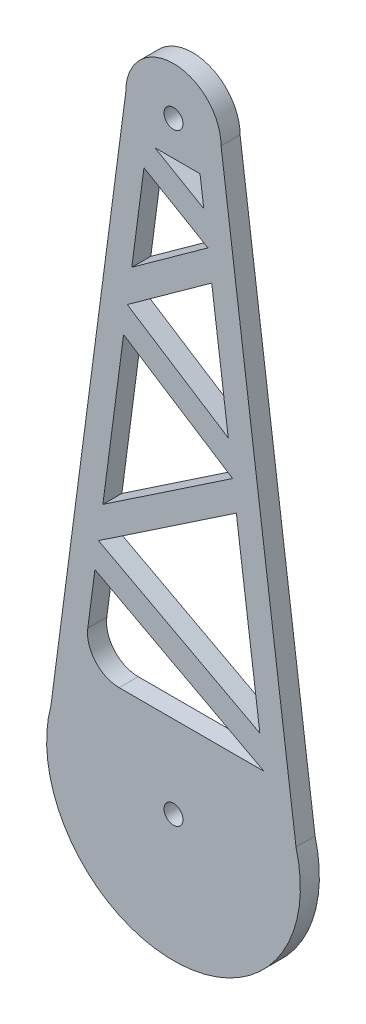
SolidWorks part; units mm, degrees
material "Alloy Steel"
ref_plane "Front Plane" through (0, 0, 0) normal (0, 0, 1) x (1, 0, 0)
ref_plane "Top Plane" through (0, 0, 0) normal (0, 1, 0) x (1, 0, 0)
ref_plane "Right Plane" through (0, 0, 0) normal (1, 0, 0) x (0, 0, -1)
sketch "Sketch1" plane through (0, 0, 0) normal (0, 0, 1) x (1, 0, 0)
  line L0 (0, 0) -> (0, 168.6185) construction
  line L1 (-19.3193, 5.1736) -> (-7.5, 95)
  line L2 (19.3193, 5.1736) -> (7.5, 95)
  line L3 (-3.4653, 95.0019) -> (-16.4704, -3.8374) construction
  line L4 (3.4839, 94.8604) -> (16.4955, -4.0277) construction
  line L5 (-14.255, 13) -> (14.255, 13)
  line L6 (-14.255, 13) -> (-12.3856, 27.2077)
  line L7 (-2.8983, 89.5344) -> (4.1847, 89.5344)
  line L8 (4.1847, 89.5344) -> (4.7742, 85.0537)
  line L9 (-12.3856, 27.2077) -> (14.255, 13)
  line L10 (-11.8282, 31.4437) -> (13.6135, 17.8754)
  line L11 (-11.1322, 36.7332) -> (-7.8666, 61.5521)
  line L12 (-11.8282, 31.4437) -> (9.9042, 46.0664)
  line L13 (-11.1322, 36.7332) -> (9.3214, 50.4954)
  line L14 (9.9042, 46.0664) -> (13.6135, 17.8754)
  line L15 (9.3214, 50.4954) -> (-7.8666, 61.5521)
  line L16 (-7.2896, 65.9371) -> (8.6377, 55.6914)
  line L17 (-7.2896, 65.9371) -> (6.027, 75.5327)
  line L18 (-6.5729, 71.3838) -> (5.4345, 80.036)
  line L19 (5.4345, 80.036) -> (-4.6589, 85.9304)
  line L20 (4.7742, 85.0537) -> (-2.8983, 89.5344)
  line L21 (-6.5729, 71.3838) -> (-4.6589, 85.9304)
  line L22 (6.027, 75.5327) -> (8.6377, 55.6914)
  arc A0 (-19.3193, 5.1736) -> (19.3193, 5.1736) centre (0, 0) ccw
  arc A1 (7.5, 95) -> (-7.5, 95) centre (0, 95) ccw
  circle A2 centre (0, 95) radius 1.5
  circle A3 centre (0, 0) radius 1.5
  dimension "D1" = 40
  dimension "D2" = 15
  dimension "D3" = 3
  dimension "D4" = 3
  dimension "D5" = 95
  dimension "D6" = 4
  dimension "D7" = 4
  dimension "D8" = 4
  dimension "D9" = 13
  dimension "D10" = 4
  dimension "D11" = 4
  dimension "D12" = 4
  dimension "D13" = 4
extrude "Boss-Extrude1" add sketch "Sketch1" along normal blind 3
fillet "Fillet1" radius 5 1 edges at (-14.255, 13, 1.5)
ref_axis "Axis1" through (0, 0, 37.8668) along (0, 0, -1)
